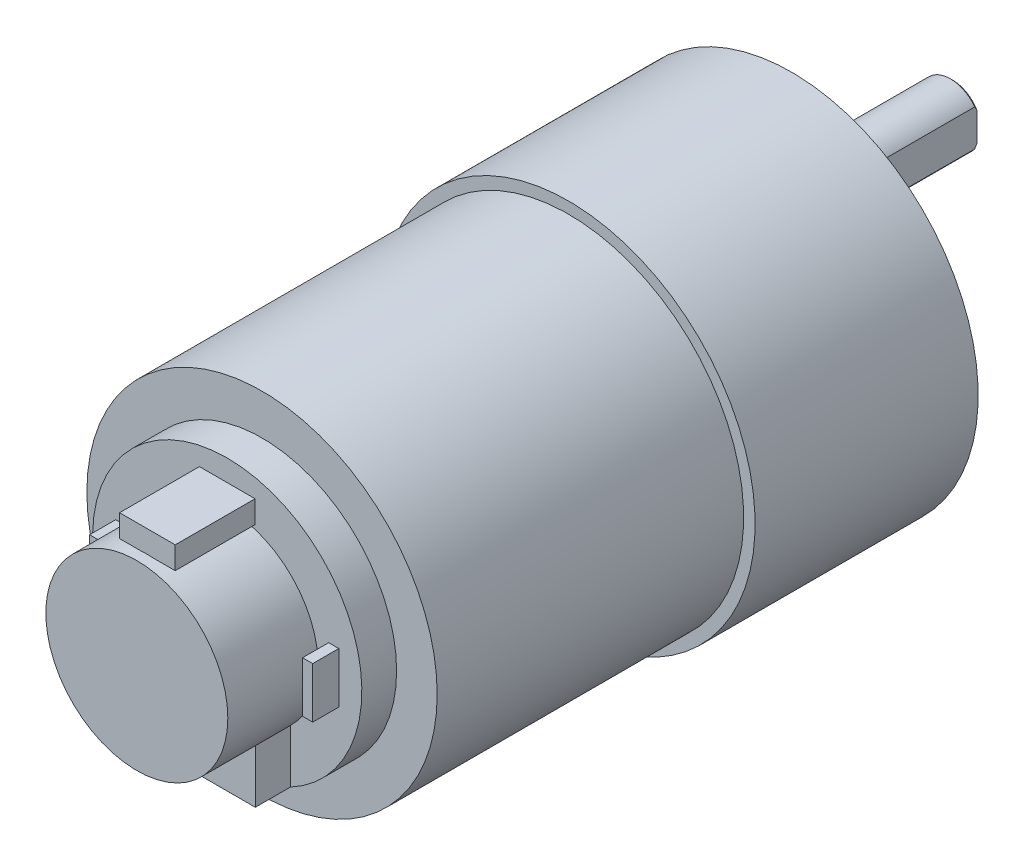
SolidWorks part; units mm, degrees
material "Plain Carbon Steel"
ref_plane "Front Plane" through (0, 0, 0) normal (0, 0, 1) x (1, 0, 0)
ref_plane "Top Plane" through (0, 0, 0) normal (0, 1, 0) x (1, 0, 0)
ref_plane "Right Plane" through (0, 0, 0) normal (1, 0, 0) x (0, 0, -1)
sketch "Sketch1" plane through (0, 0, 0) normal (0, 0, 1) x (1, 0, 0)
  line L0 (0, 0) -> (-7, 0)
  line L1 (0, 0) -> (-17.272, 0)
  line L2 (0, 0) -> (0, 17.272)
  line L3 (0, 0) -> (0, -15.5)
  line L4 (-4.6, 1.8) -> (-4.6, -1.8)
  line L5 (0, 0) -> (0, -15.5) construction
  circle A0 centre (0, 0) radius 17.272
  circle A1 centre (-7, 0) radius 3
  circle A2 centre (-7, 0) radius 6
  circle A3 centre (0, -15.5) radius 1.5
  circle A4 centre (-13.4234, -7.75) radius 1.5
  circle A5 centre (-13.4234, 7.75) radius 1.5
  circle A6 centre (0, 15.5) radius 1.5
  circle A7 centre (13.4234, 7.75) radius 1.5
  circle A8 centre (13.4234, -7.75) radius 1.5
  point P28 (0, -0.9391)
  point P31 (0, 0)
  point P35 (0, 0)
  dimension "D1" = 34.544
  dimension "D2" = 7
  dimension "D4" = 6
  dimension "D3" = 12
  dimension "D8" = 6
  dimension "D6" = 15.5
  dimension "D7" = 3
  dimension "D5" = 2.4
  dimension "D9" = 15.5
extrude "Boss-Extrude1" add sketch "Sketch1" along normal blind 52.22 contours A0
extrude "Boss-Extrude2" add sketch "Sketch1<3>" against normal blind 6.5 contours A2 A1 | L4 A1 L1 | L1 A1 L4 | L1 A2 A1 | L1 A1 L4 | L4 A1 L1 region at (-7, -5.8658, 0) region at (-2.5, 0.1342, 0) region at (-4.3578, -0.685, 0) region at (-4.3578, 0.685, 0) region at (-7.1451, -1.3055, 0) region at (-7.1451, 1.3055, 0)
sketch "Sketch1<3>" plane through (0, 0, 0) normal (0, 0, 1) x (1, 0, 0) same geometry as "Sketch1"
extrude "Boss-Extrude3" add sketch "Sketch1<4>" against normal blind 22.86 contours L4 A1 L1 | L1 A1 L4 region at (-7.1451, -1.3055, 0) region at (-7.1451, 1.3055, 0)
sketch "Sketch1<4>" plane through (0, 0, 0) normal (0, 0, 1) x (1, 0, 0) same geometry as "Sketch1"
extrude "Boss-Extrude4" add sketch "Sketch1<5>" against normal blind 10.668 contours L4 A1 | L4 A1 L1 region at (-4.3578, -0.685, 0) region at (-4.3578, 0.685, 0)
sketch "Sketch1<5>" plane through (0, 0, 0) normal (0, 0, 1) x (1, 0, 0) same geometry as "Sketch1"
sketch "Sketch2" plane through (0, 0, 52.22) normal (0, 0, 1) x (1, 0, 0)
  line L0 (0, 17.272) -> (0, -17.272) construction
  line L1 (17.272, 0) -> (-17.272, 0) construction
  line L2 (-11, 2.5) -> (-10, 2.5)
  line L3 (-11, 2.5) -> (-11, -2.5)
  line L4 (-11, -2.5) -> (-10, -2.5)
  line L5 (-10, 2.5) -> (-10, -2.5)
  line L6 (10, 2.5) -> (10, -2.5)
  line L7 (11, -2.5) -> (10, -2.5)
  line L8 (11, 2.5) -> (11, -2.5)
  line L9 (11, 2.5) -> (10, 2.5)
  circle A0 centre (0, 0) radius 17.272 construction
  dimension "D1" = 5
  dimension "D2" = 1
  dimension "D3" = 2.5
  dimension "D4" = 10
extrude "Boss-Extrude5" add sketch "Sketch2" along normal blind 6
sketch "Sketch4" plane through (0, 0, 0) normal (0, 0, -1) x (-1, 0, 0)
  circle A0 centre (0, 0) radius 18.4
  dimension "D1" = 36.8
extrude "Boss-Extrude6" add sketch "Sketch4" against normal blind 22
hole_wizard "Tap Drill for M3 Tap1" positions "Sketch8" profile "Sketch7" hole size "M3" standard "ISO"
sketch "Sketch8" plane through (0, 0, 0) normal (0, 0, -1) x (-1, 0, 0)
  point P0 (-13.4234, -7.75)
  point P3 (0, -15.5)
  point P6 (0, 15.5)
  point P9 (13.4234, 7.75)
  point P12 (13.4234, -7.75)
  point P15 (-13.4234, 7.75)
sketch "Sketch7" plane through (13.4234, -7.75, 0) normal (1, 0, 0) x (0, 1, 0)
  line L0 (0, 0) -> (0, 3.7511)
  line L1 (0, 3.7511) -> (1.25, 3)
  line L2 (1.25, 3) -> (1.25, 0)
  line L5 (1.25, 0) -> (0, 0)
  line L10 (0, 3.7511) -> (-1.25, 3) construction
  line L11 (0, -6.35) -> (0, 107.95) construction
  dimension "Hole Dia." = 2.5
  dimension "Hole Depth" = 3
  dimension "Drill Angle" = 118
sketch "Sketch9" plane through (0, 0, 52.22) normal (0, 0, 1) x (1, 0, 0)
  circle A0 centre (0, 0) radius 13.2715
  dimension "D1" = 26.543
extrude "Boss-Extrude7" add sketch "Sketch9" along normal blind 3.429
sketch "Sketch10" plane through (0, 0, 55.649) normal (0, 0, 1) x (1, 0, 0)
  circle A0 centre (0, 0) radius 8.9726
  dimension "D1" = 17.9451
extrude "Boss-Extrude8" add sketch "Sketch10" along normal blind 8.9154
sketch "Sketch11" plane through (0, 0, 55.649) normal (0, 0, 1) x (1, 0, 0)
  line L1 (6.223, -11.7221) -> (-6.223, -11.7221)
  line L2 (6.223, -11.7221) -> (6.223, -5.6769)
  line L3 (6.223, -5.6769) -> (-6.223, -5.6769)
  line L4 (-6.223, -11.7221) -> (-6.223, -5.6769)
  circle A0 centre (0, 0) radius 13.2715 construction
  circle A1 centre (0, 0) radius 13.2715 construction
  dimension "D1" = 6.0452
  dimension "D2" = 12.446
extrude "Boss-Extrude9" add sketch "Sketch11" along normal blind 3.4544
sketch "Sketch12" plane through (0, 0, 55.649) normal (0, 0, 1) x (1, 0, 0)
  line L1 (2.7432, 8.9535) -> (-2.7432, 8.9535)
  line L2 (2.7432, 8.9535) -> (2.7432, 11.1633)
  line L3 (2.7432, 11.1633) -> (-2.7432, 11.1633)
  line L4 (-2.7432, 8.9535) -> (-2.7432, 11.1633)
  arc A1 (6.223, -11.7221) -> (-6.223, -11.7221) centre (0, 0) ccw construction
  point P4 (0, 13.2715)
  point P5 (0, 11.1633)
  dimension "D1" = 5.4864
  dimension "D2" = 2.2098
  dimension "D3" = 4.318
extrude "Boss-Extrude10" add sketch "Sketch12" along normal blind 7.874
chamfer "Chamfer1" distance 0.2 angle 45 1 edges at (-10, 0, -22.86)
chamfer "Chamfer2" distance 0.5 angle 45 1 edges at (-1, 0, -6.5)
